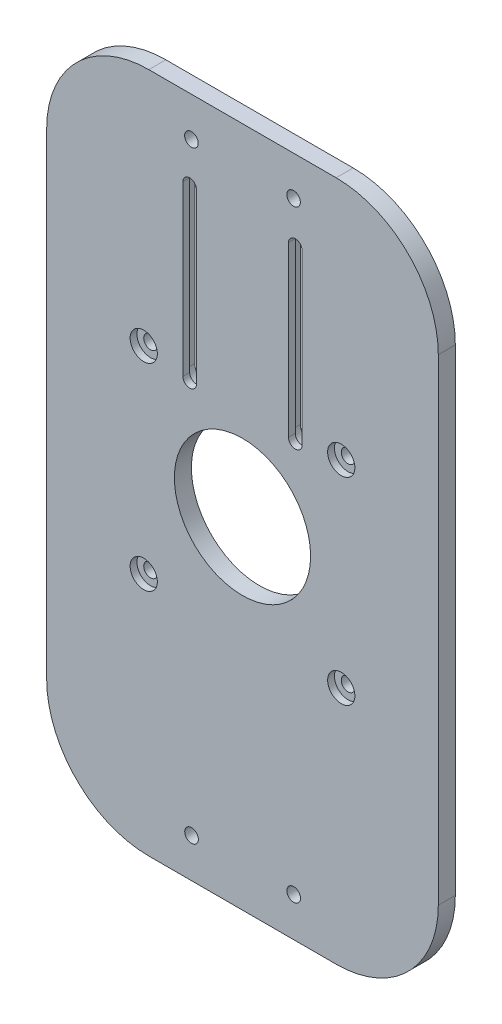
SolidWorks part; units mm, degrees
ref_plane "Front Plane" through (0, 0, 0) normal (1, 0, 0) x (0, 1, 0)
ref_plane "Top Plane" through (0, 0, 0) normal (0, 0, 1) x (0, 1, 0)
ref_plane "Right Plane" through (0, 0, 0) normal (0, 1, 0) x (-1, 0, 0)
sketch "Sketch1" plane through (0, 0, 0) normal (0, 0, 1) x (0, 1, 0)
  line L1 (-100, -57.5) -> (100, -57.5)
  line L2 (-100, -57.5) -> (-100, 57.5)
  line L3 (-100, 57.5) -> (100, 57.5)
  line L4 (100, -57.5) -> (100, 57.5)
  line L5 (-100, -57.5) -> (100, 57.5) construction
  line L6 (-100, 57.5) -> (100, -57.5) construction
  circle A0 centre (0, 0) radius 20
  point P0 (0, 0)
  dimension "D3" = 40
  dimension "D1" = 115
  dimension "D2" = 200
extrude "Boss-Extrude1" add sketch "Sketch1" along normal blind 5
sketch "Sketch4" plane through (0, 0, 5) normal (0, 0, 1) x (1, 0, 0)
  line L0 (0, 100) -> (0, -100) construction
  line L1 (57.5, 100) -> (-57.5, 100) construction
  line L2 (-57.5, -100) -> (57.5, -100) construction
  line L3 (-57.5, 0) -> (57.5, 0) construction
  line L4 (-57.5, 100) -> (-57.5, -100) construction
  line L5 (57.5, -100) -> (57.5, 100) construction
  circle A0 centre (29, 29) radius 2 construction
  circle A1 centre (-29, 29) radius 2 construction
  circle A2 centre (-29, -29) radius 2 construction
  circle A3 centre (29, -29) radius 2 construction
  circle A4 centre (29, 29) radius 2
  circle A5 centre (-29, 29) radius 2
  circle A6 centre (-29, -29) radius 2
  circle A7 centre (29, -29) radius 2
extrude "Cut-Extrude1" cut sketch "Sketch4" against normal up to next
sketch "Sketch5" plane through (0, 0, 5) normal (0, 0, 1) x (1, 0, 0)
  circle A0 centre (29, 29) radius 2 construction
  circle A1 centre (29, -29) radius 2 construction
  circle A3 centre (-29, 29) radius 2 construction
  circle A6 centre (-29, -29) radius 2 construction
  circle A40 centre (-29, -29) radius 2 construction
  circle A41 centre (-29, 29) radius 2 construction
  circle A42 centre (29, -29) radius 2 construction
  circle A43 centre (29, 29) radius 2 construction
  circle A44 centre (-29, -29) radius 4
  circle A45 centre (-29, 29) radius 4
  circle A46 centre (29, -29) radius 4
  circle A47 centre (29, 29) radius 4
  dimension "D1" = 2
extrude "Cut-Extrude2" cut sketch "Sketch5" against normal blind 2
fillet "Fillet1" radius 30 4 edges at (57.5, 100, 2.5) (-57.5, 100, 2.5) (-57.5, -100, 2.5) (57.5, -100, 2.5)
sketch "Sketch8" plane through (0, 0, 5) normal (0, 0, 1) x (1, 0, 0)
  circle A0 centre (15, 88.5) radius 2
  circle A1 centre (-15, 88.5) radius 2
  circle A2 centre (-14.9609, -88.5) radius 2
  circle A3 centre (15.0391, -88.5) radius 2
extrude "Cut-Extrude4" cut sketch "Sketch8" against normal through all
sketch "Sketch9" plane through (0, 0, 5) normal (0, 0, 1) x (1, 0, 0)
  line L0 (0, 0) -> (0, 100) construction
  line L1 (27.5, 100) -> (-27.5, 100) construction
  line L2 (-15.5, 76.5) -> (-15.5, 26.6053) construction
  line L3 (-17.5, 76.5) -> (-17.5, 27)
  line L4 (-13.5, 76.5) -> (-13.5, 27)
  line L5 (15.5, 76.5) -> (15.5, 26.6053) construction
  line L6 (17.5, 76.5) -> (17.5, 27)
  line L7 (13.5, 76.5) -> (13.5, 27)
  arc A0 (-17.5, 76.5) -> (-13.5, 76.5) centre (-15.5, 76.5) cw
  arc A1 (-17.5, 27) -> (-13.5, 27) centre (-15.5, 27) ccw
  arc A2 (17.5, 76.5) -> (13.5, 76.5) centre (15.5, 76.5) ccw
  arc A3 (17.5, 27) -> (13.5, 27) centre (15.5, 27) cw
  circle A6 centre (-15, 88.5) radius 2 construction
  circle A11 centre (0, 0) radius 20 construction
  dimension "D3" = 10
  dimension "D4" = 2
  dimension "D5" = 5
  dimension "D1" = 31
  dimension "D2" = 4
extrude "Cut-Extrude5" cut sketch "Sketch9" against normal through all
sketch "Sketch10" plane through (0, 0, 0) normal (0, 0, -1) x (1, 0, 0)
  line L58 (0, 0) -> (0, -100) construction
  line L59 (27.5, -100) -> (-27.5, -100) construction
  line L60 (-12, -76.5) -> (-12, -27)
  line L61 (-19, -27) -> (-19, -76.5)
  line L62 (-12, -76.5) -> (-12, -27)
  line L63 (-19, -27) -> (-19, -76.5)
  line L64 (12, -76.5) -> (12, -27)
  line L65 (19, -27) -> (19, -76.5)
  arc A48 (19, -76.5) -> (12, -76.5) centre (15.5, -76.5) cw
  arc A49 (12, -27) -> (19, -27) centre (15.5, -27) cw
  arc A50 (-12, -27) -> (-19, -27) centre (-15.5, -27) ccw
  arc A51 (-19, -76.5) -> (-12, -76.5) centre (-15.5, -76.5) ccw
  arc A52 (-12, -27) -> (-19, -27) centre (-15.5, -27) ccw
  arc A53 (-19, -76.5) -> (-12, -76.5) centre (-15.5, -76.5) ccw
  dimension "D1" = 1.5
extrude "Cut-Extrude6" cut sketch "Sketch10" against normal blind 3
